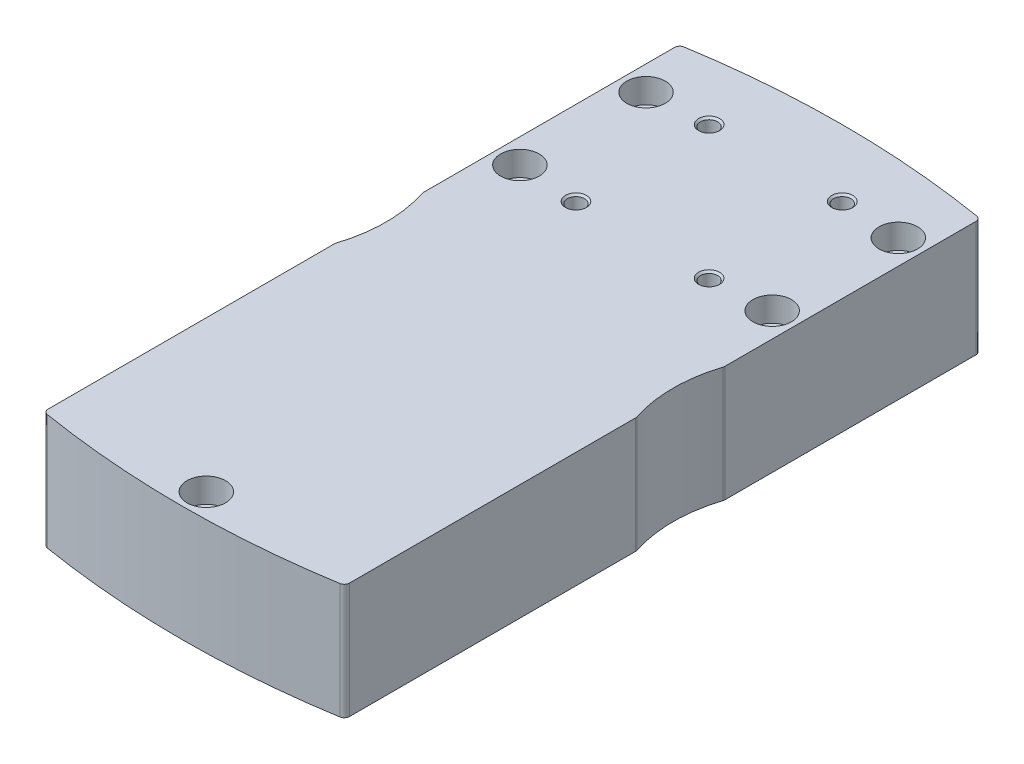
SolidWorks part; units mm, degrees
ref_plane "Front Plane" through (0, 0, 0) normal (0, 0, 1) x (1, 0, 0)
ref_plane "Top Plane" through (0, 0, 0) normal (0, 1, 0) x (1, 0, 0)
ref_plane "Right Plane" through (0, 0, 0) normal (1, 0, 0) x (0, 0, -1)
sketch "Sketch1" plane through (0, 0, 0) normal (0, 1, 0) x (1, 0, 0)
  line L0 (-43, 86.5221) -> (-43, 4.8795)
  line L1 (43, 4.8795) -> (43, 86.5221)
  line L2 (43, 111.9779) -> (43, 183.6205)
  line L3 (-43, 183.6205) -> (-43, 111.9779)
  arc A0 (-43, 4.8795) -> (-41.7427, 3.3992) centre (-41.5, 4.8795) ccw
  arc A1 (-41.7427, 3.3992) -> (41.7427, 3.3992) centre (0, 258) ccw
  arc A2 (41.7427, 3.3992) -> (43, 4.8795) centre (41.5, 4.8795) ccw
  arc A3 (43, 86.5221) -> (42.9277, 86.9821) centre (41.5, 86.5221) ccw
  arc A4 (42.9277, 86.9821) -> (42.9277, 111.5179) centre (81, 99.25) cw
  arc A5 (42.9277, 111.5179) -> (43, 111.9779) centre (41.5, 111.9779) ccw
  arc A6 (43, 183.6205) -> (41.7427, 185.1008) centre (41.5, 183.6205) ccw
  arc A7 (41.7427, 185.1008) -> (-41.7427, 185.1008) centre (0, -69.5) ccw
  arc A8 (-41.7427, 185.1008) -> (-43, 183.6205) centre (-41.5, 183.6205) ccw
  arc A9 (-43, 111.9779) -> (-42.9277, 111.5179) centre (-41.5, 111.9779) ccw
  arc A10 (-42.9277, 111.5179) -> (-42.9277, 86.9821) centre (-81, 99.25) cw
  arc A11 (-42.9277, 86.9821) -> (-43, 86.5221) centre (-41.5, 86.5221) ccw
extrude "Boss-Extrude1" add sketch "Sketch1" along normal blind 33
sketch "Sketch2" plane through (0, 0, 0) normal (0, 1, 0) x (1, 0, 0)
  line L0 (27.5, 62.2741) -> (27.5, 101.2846)
  line L1 (25.8923, 107.2846) -> (16.1077, 124.2321)
  line L2 (14.5, 130.2321) -> (14.5, 166)
  line L3 (-14.5, 166) -> (-14.5, 130.2321)
  line L4 (-16.1077, 124.2321) -> (-25.8923, 107.2846)
  line L5 (-27.5, 101.2846) -> (-27.5, 62.2741)
  arc A0 (-28.2143, 58.1958) -> (28.2143, 58.1958) centre (0, 48) ccw
  arc A1 (28.2143, 58.1958) -> (27.5, 62.2741) centre (39.5, 62.2741) cw
  arc A2 (27.5, 101.2846) -> (25.8923, 107.2846) centre (15.5, 101.2846) ccw
  arc A3 (16.1077, 124.2321) -> (14.5, 130.2321) centre (26.5, 130.2321) cw
  arc A4 (14.5, 166) -> (-14.5, 166) centre (0, 166) ccw
  arc A5 (-14.5, 130.2321) -> (-16.1077, 124.2321) centre (-26.5, 130.2321) cw
  arc A6 (-25.8923, 107.2846) -> (-27.5, 101.2846) centre (-15.5, 101.2846) ccw
  arc A7 (-27.5, 62.2741) -> (-28.2143, 58.1958) centre (-39.5, 62.2741) cw
extrude "Cut-Extrude1" cut sketch "Sketch2" along normal blind 29
sketch "Sketch3" plane through (0, 0, 0) normal (0, 1, 0) x (1, 0, 0)
  arc A0 (-15.3032, 170.269) -> (15.3032, 170.269) centre (0, 150.5) ccw
  arc A1 (15.3032, 170.269) -> (12.3927, 173.528) centre (22.6487, 179.7581) cw
  arc A2 (12.3927, 173.528) -> (-12.3927, 173.528) centre (0, 166) ccw
  arc A3 (-12.3927, 173.528) -> (-15.3032, 170.269) centre (-22.6487, 179.7581) cw
extrude "Cut-Extrude2" cut sketch "Sketch3" along normal blind 10
sketch "Sketch4" plane through (0, 0, 0) normal (0, 1, 0) x (1, 0, 0)
  line L0 (27.5, 61.9194) -> (27.5, 136.5806)
  line L1 (-27.5, 136.5806) -> (-27.5, 61.9194)
  arc A0 (-28.125, 58.4396) -> (28.125, 58.4396) centre (0, 48) ccw
  arc A1 (28.125, 58.4396) -> (27.5, 61.9194) centre (37.5, 61.9194) cw
  arc A2 (27.5, 136.5806) -> (28.125, 140.0604) centre (37.5, 136.5806) cw
  arc A3 (28.125, 140.0604) -> (-28.125, 140.0604) centre (0, 150.5) ccw
  arc A4 (-28.125, 140.0604) -> (-27.5, 136.5806) centre (-37.5, 136.5806) cw
  arc A5 (-27.5, 61.9194) -> (-28.125, 58.4396) centre (-37.5, 61.9194) cw
extrude "Cut-Extrude3" cut sketch "Sketch4" along normal blind 3
sketch "Sketch5" plane through (0, 0, 0) normal (1, 0, 0) x (0, 0, -1)
  line L0 (7, 33) -> (12.5, 33)
  line L1 (12.5, 33) -> (12.5, 26)
  line L2 (12.5, 26) -> (10.3, 26)
  line L3 (10.3, 26) -> (10.3, 0)
  line L4 (10.3, 0) -> (7, 0)
  line L5 (7, 0) -> (7, 33)
  line L6 (7, 0) -> (7, 33) construction
revolve "Cut-Revolve1" cut sketch "Sketch5" angle 360 about L6 reverse direction yes
ref_plane "Plane1" through (36, 0, 0) normal (1, 0, 0) x (0, 0, -1)
sketch "Sketch6" plane through (36, 0, 0) normal (1, 0, 0) x (0, 0, -1)
  line L0 (132.5, 33) -> (138, 33)
  line L1 (138, 33) -> (138, 26)
  line L2 (138, 26) -> (135.8, 26)
  line L3 (135.8, 26) -> (135.8, 0)
  line L4 (135.8, 0) -> (132.5, 0)
  line L5 (132.5, 0) -> (132.5, 33)
  line L6 (132.5, 0) -> (132.5, 33) construction
revolve "Cut-Revolve2" cut sketch "Sketch6" angle 360 about L6 reverse direction yes
sketch "Sketch7" plane through (36, 0, 0) normal (1, 0, 0) x (0, 0, -1)
  line L0 (168.5, 33) -> (174, 33)
  line L1 (174, 33) -> (174, 26)
  line L2 (174, 26) -> (171.8, 26)
  line L3 (171.8, 26) -> (171.8, 0)
  line L4 (171.8, 0) -> (168.5, 0)
  line L5 (168.5, 0) -> (168.5, 33)
  line L6 (168.5, 0) -> (168.5, 33) construction
revolve "Cut-Revolve3" cut sketch "Sketch7" angle 360 about L6 reverse direction yes
ref_plane "Plane2" through (-36, 0, 0) normal (1, 0, 0) x (0, 0, -1)
sketch "Sketch8" plane through (-36, 0, 0) normal (1, 0, 0) x (0, 0, -1)
  line L0 (132.5, 33) -> (138, 33)
  line L1 (138, 33) -> (138, 26)
  line L2 (138, 26) -> (135.8, 26)
  line L3 (135.8, 26) -> (135.8, 0)
  line L4 (135.8, 0) -> (132.5, 0)
  line L5 (132.5, 0) -> (132.5, 33)
  line L6 (132.5, 0) -> (132.5, 33) construction
revolve "Cut-Revolve4" cut sketch "Sketch8" angle 360 about L6 reverse direction yes
sketch "Sketch9" plane through (-36, 0, 0) normal (1, 0, 0) x (0, 0, -1)
  line L0 (168.5, 33) -> (174, 33)
  line L1 (174, 33) -> (174, 26)
  line L2 (174, 26) -> (171.8, 26)
  line L3 (171.8, 26) -> (171.8, 0)
  line L4 (171.8, 0) -> (168.5, 0)
  line L5 (168.5, 0) -> (168.5, 33)
  line L6 (168.5, 0) -> (168.5, 33) construction
revolve "Cut-Revolve5" cut sketch "Sketch9" angle 360 about L6 reverse direction yes
ref_plane "Plane3" through (0, 0, -169.5) normal (0, 0, 1) x (1, 0, 0)
sketch "Sketch10" plane through (0, 0, -169.5) normal (0, 0, 1) x (1, 0, 0)
  line L0 (19, 33) -> (22, 33)
  line L1 (22, 33) -> (21.4585, 32.4585)
  line L2 (21.4585, 32.4585) -> (21.4585, 14)
  line L3 (21.4585, 14) -> (19, 12.5806)
  line L4 (19, 12.5806) -> (19, 33)
  line L5 (19, 12.5806) -> (19, 33) construction
revolve "Cut-Revolve6" cut sketch "Sketch10" angle 360 about L5 reverse direction yes
cosmetic thread "Cosmetic Thread1" parameters "D1"=16, "D2"=6
sketch "Sketch11" plane through (0, 0, -169.5) normal (0, 0, 1) x (1, 0, 0)
  line L0 (-19, 33) -> (-16, 33)
  line L1 (-16, 33) -> (-16.5415, 32.4585)
  line L2 (-16.5415, 32.4585) -> (-16.5415, 14)
  line L3 (-16.5415, 14) -> (-19, 12.5806)
  line L4 (-19, 12.5806) -> (-19, 33)
  line L5 (-19, 12.5806) -> (-19, 33) construction
revolve "Cut-Revolve7" cut sketch "Sketch11" angle 360 about L5 reverse direction yes
cosmetic thread "Cosmetic Thread2" parameters "D1"=16, "D2"=6
ref_plane "Plane4" through (0, 0, -131.5) normal (0, 0, 1) x (1, 0, 0)
sketch "Sketch12" plane through (0, 0, -131.5) normal (0, 0, 1) x (1, 0, 0)
  line L0 (19, 33) -> (22, 33)
  line L1 (22, 33) -> (21.4585, 32.4585)
  line L2 (21.4585, 32.4585) -> (21.4585, 14)
  line L3 (21.4585, 14) -> (19, 12.5806)
  line L4 (19, 12.5806) -> (19, 33)
  line L5 (19, 12.5806) -> (19, 33) construction
revolve "Cut-Revolve8" cut sketch "Sketch12" angle 360 about L5 reverse direction yes
cosmetic thread "Cosmetic Thread3" parameters "D1"=16, "D2"=6
sketch "Sketch13" plane through (0, 0, -131.5) normal (0, 0, 1) x (1, 0, 0)
  line L0 (-19, 33) -> (-16, 33)
  line L1 (-16, 33) -> (-16.5415, 32.4585)
  line L2 (-16.5415, 32.4585) -> (-16.5415, 14)
  line L3 (-16.5415, 14) -> (-19, 12.5806)
  line L4 (-19, 12.5806) -> (-19, 33)
  line L5 (-19, 12.5806) -> (-19, 33) construction
revolve "Cut-Revolve9" cut sketch "Sketch13" angle 360 about L5 reverse direction yes
cosmetic thread "Cosmetic Thread4" parameters "D1"=16, "D2"=6
ref_plane "Plane5" through (0, 26, 0) normal (0, 1, 0) x (1, 0, 0)
ref_plane "Plane6" through (0, 0, -150.5) normal (0, 0, 1) x (1, 0, 0)
ref_plane "ANBAU XY" through (0, 0, 0) normal (0, 1, 0) x (1, 0, 0)
ref_plane "ANBAU XZ" through (0, 0, -150.5) normal (0, 0, 1) x (1, 0, 0)
ref_plane "ANBAU YZ" through (0, 0, 0) normal (1, 0, 0) x (0, 0, -1)
ref_axis "ANBAU X" through (-80.9, 0, -150.5) along (1, 0, 0)
ref_axis "ANBAU Y" through (0, 0, 50) along (0, 0, -1)
ref_axis "ANBAU Z" through (0, 50, -150.5) along (0, -1, 0)
sketch3d "ANBAU"
  point P0 (0, 0, -150.5)
ref_plane "S1 1 XY" through (0, 26, 0) normal (0, 1, 0) x (1, 0, 0)
ref_plane "S1 1 XZ" through (0, 0, -168.5) normal (0, 0, 1) x (1, 0, 0)
ref_plane "S1 1 YZ" through (36, 0, 0) normal (1, 0, 0) x (0, 0, -1)
ref_axis "S1 1 X" through (-80.9, 26, -168.5) along (1, 0, 0)
ref_axis "S1 1 Y" through (36, 26, 50) along (0, 0, -1)
ref_axis "S1 1 Z" through (36, 50, -168.5) along (0, -1, 0)
sketch3d "S1 1"
  point P0 (36, 26, -168.5)
ref_plane "S1 2 XY" through (0, 26, 0) normal (0, 1, 0) x (1, 0, 0)
ref_plane "S1 2 XZ" through (0, 0, -132.5) normal (0, 0, 1) x (1, 0, 0)
ref_plane "S1 2 YZ" through (36, 0, 0) normal (1, 0, 0) x (0, 0, -1)
ref_axis "S1 2 X" through (-80.9, 26, -132.5) along (1, 0, 0)
ref_axis "S1 2 Y" through (36, 26, 50) along (0, 0, -1)
ref_axis "S1 2 Z" through (36, 50, -132.5) along (0, -1, 0)
sketch3d "S1 2"
  point P0 (36, 26, -132.5)
ref_plane "S2 1 XY" through (0, 26, 0) normal (0, 1, 0) x (1, 0, 0)
ref_plane "S2 1 XZ" through (0, 0, -168.5) normal (0, 0, 1) x (1, 0, 0)
ref_plane "S2 1 YZ" through (-36, 0, 0) normal (1, 0, 0) x (0, 0, -1)
ref_axis "S2 1 X" through (-80.9, 26, -168.5) along (1, 0, 0)
ref_axis "S2 1 Y" through (-36, 26, 50) along (0, 0, -1)
ref_axis "S2 1 Z" through (-36, 50, -168.5) along (0, -1, 0)
sketch3d "S2 1"
  point P0 (-36, 26, -168.5)
ref_plane "S2 2 XY" through (0, 26, 0) normal (0, 1, 0) x (1, 0, 0)
ref_plane "S2 2 XZ" through (0, 0, -132.5) normal (0, 0, 1) x (1, 0, 0)
ref_plane "S2 2 YZ" through (-36, 0, 0) normal (1, 0, 0) x (0, 0, -1)
ref_axis "S2 2 X" through (-80.9, 26, -132.5) along (1, 0, 0)
ref_axis "S2 2 Y" through (-36, 26, 50) along (0, 0, -1)
ref_axis "S2 2 Z" through (-36, 50, -132.5) along (0, -1, 0)
sketch3d "S2 2"
  point P0 (-36, 26, -132.5)
ref_plane "S3 XY" through (0, 26, 0) normal (0, 1, 0) x (1, 0, 0)
ref_plane "S3 XZ" through (0, 0, -7) normal (0, 0, 1) x (1, 0, 0)
ref_plane "S3 YZ" through (0, 0, 0) normal (1, 0, 0) x (0, 0, -1)
ref_axis "S3 X" through (-80.9, 26, -7) along (1, 0, 0)
ref_axis "S3 Y" through (0, 26, 50) along (0, 0, -1)
ref_axis "S3 Z" through (0, 50, -7) along (0, -1, 0)
sketch3d "S3"
  point P0 (0, 26, -7)
other "Freeze***"
